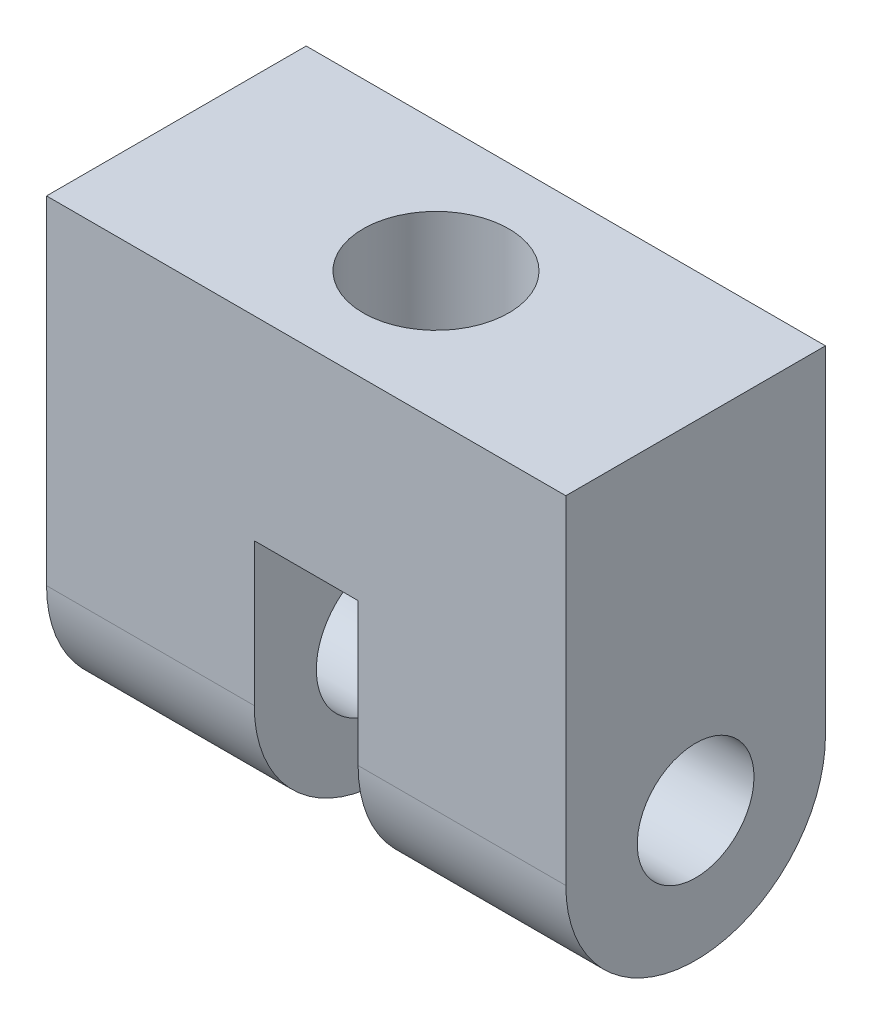
SolidWorks part; units mm, degrees
ref_plane "Front Plane" through (0, 0, 0) normal (0, 0, 1) x (1, 0, 0)
ref_plane "Top Plane" through (0, 0, 0) normal (0, 1, 0) x (1, 0, 0)
ref_plane "Right Plane" through (0, 0, 0) normal (1, 0, 0) x (0, 0, -1)
sketch "Sketch1" plane through (0, 0, 0) normal (0, 1, 0) x (1, 0, 0)
  line L1 (-10, -5) -> (10, -5)
  line L2 (-10, -5) -> (-10, 5)
  line L3 (-10, 5) -> (10, 5)
  line L4 (10, -5) -> (10, 5)
  line L5 (-10, -5) -> (10, 5) construction
  line L6 (-10, 5) -> (10, -5) construction
  point P0 (0, 0)
  dimension "D1" = 20
  dimension "D2" = 10
extrude "Boss-Extrude1" add sketch "Sketch1" along normal blind 18
sketch "Sketch2" plane through (0, 0, 0) normal (0, 0, 1) x (1, 0, 0)
  line L0 (-10, 0) -> (10, 0) construction
  line L1 (2, 10.5) -> (-2, 10.5)
  line L2 (2, 10.5) -> (2, 0)
  line L3 (2, 0) -> (-2, 0)
  line L4 (-2, 10.5) -> (-2, 0)
  line L5 (2, 10.5) -> (-2, 0) construction
  line L6 (2, 0) -> (-2, 10.5) construction
  point P0 (0, 5.25)
  dimension "D1" = 4
  dimension "D2" = 10.5
extrude "Cut-Extrude1" cut sketch "Sketch2" against normal through all both and the other way through all
hole_wizard "#16 (0.177) Diameter Hole1" positions "Sketch3" profile "Sketch4" hole size "#16" standard "ANSI Inch" end condition up to next
sketch "Sketch3" plane through (10, 0, 0) normal (1, 0, 0) x (0, 0, -1)
  point P0 (0, 5)
  dimension "D1" = 5
sketch "Sketch4" plane through (10, 5, 0) normal (0, 1, 0) x (0, 0, -1)
  line L0 (0, 0) -> (0, 8)
  line L1 (0, 8) -> (2.2479, 8)
  line L2 (2.2479, 8) -> (2.2479, 0)
  line L5 (2.2479, 0) -> (0, 0)
  line L11 (0, -6.35) -> (0, 107.95) construction
  dimension "Thru Hole Dia." = 4.4958
  dimension "Thru Hole Depth" = 8
hole_wizard "#5 (0.2055) Diameter Hole1" positions "Sketch5" profile "Sketch6" hole size "#5" standard "ANSI Inch" end condition up to next
sketch "Sketch5" plane through (-2, 0, 0) normal (1, 0, 0) x (0, 0, -1)
  point P0 (0, 5)
sketch "Sketch6" plane through (-2, 5, 0) normal (0, 1, 0) x (0, 0, -1)
  line L0 (0, 0) -> (0, 8)
  line L1 (0, 8) -> (2.6098, 8)
  line L2 (2.6098, 8) -> (2.6098, 0)
  line L5 (2.6098, 0) -> (0, 0)
  line L11 (0, -6.35) -> (0, 107.95) construction
  dimension "Thru Hole Dia." = 5.2197
  dimension "Thru Hole Depth" = 8
hole_wizard "#2 (0.221) Diameter Hole1" positions "Sketch7" profile "Sketch8" hole size "#2" standard "ANSI Inch"
sketch "Sketch7" plane through (0, 18, 0) normal (0, 1, 0) x (1, 0, 0)
  point P0 (0, 0)
sketch "Sketch8" plane through (0, 18, 0) normal (1, 0, 0) x (0, 0, 1)
  line L0 (0, 0) -> (0, 9.8144)
  line L1 (0, 9.8144) -> (2.8067, 8.128)
  line L2 (2.8067, 8.128) -> (2.8067, 0)
  line L5 (2.8067, 0) -> (0, 0)
  line L10 (0, 9.8144) -> (-2.8067, 8.128) construction
  line L11 (0, -6.35) -> (0, 107.95) construction
  dimension "Hole Dia." = 5.6134
  dimension "Hole Depth" = 8.128
  dimension "Drill Angle" = 118
fillet "Fillet2" 2 edges at (-6, 0, 5) (-6, 0, -5) type full round first side face at (0, 7.125, 5) second side face at (0, 7.125, -5) middle face at (-6, 0, 0)
fillet "Fillet3" 2 edges at (6, 0, 5) (6, 0, -5) type full round first side face at (0, 8.375, 5) second side face at (0, 8.375, -5) middle face at (6, 0, 0)
equation "\"t\"=10"
equation "\"D2@Sketch1\"=\"t\""
equation "\"D1@Sketch3\"=\"t\"/2"
equation "\"D2@Sketch2\"=\"t\"*1.05"
